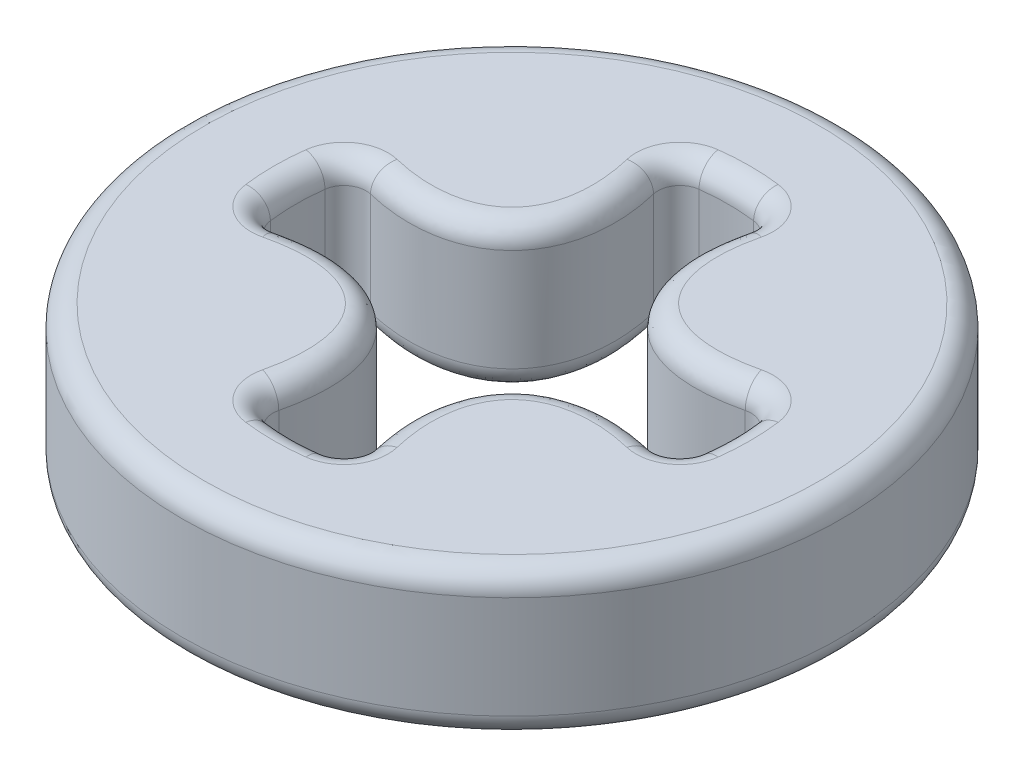
SolidWorks part; units mm, degrees
ref_plane "Front Plane" through (0, 0, 0) normal (0, 0, 1) x (1, 0, 0)
ref_plane "Top Plane" through (0, 0, 0) normal (0, 1, 0) x (1, 0, 0)
ref_plane "Right Plane" through (0, 0, 0) normal (1, 0, 0) x (0, 0, -1)
sketch "Sketch4" plane through (0, 0, 0) normal (0, 1, 0) x (1, 0, 0)
  circle A0 centre (0, 0) radius 4.5
extrude "Boss-Extrude3" add sketch "Sketch4" along normal blind 2
sketch "Sketch3" plane through (0, 0, 0) normal (0, 1, 0) x (1, 0, 0)
  arc A0 (0.7152, 2.862) -> (-0.7152, 2.862) centre (0, 0) ccw
  arc A1 (-2.862, 0.7152) -> (-2.862, -0.7152) centre (0, 0) ccw
  arc A2 (-0.7152, -2.862) -> (0.7152, -2.862) centre (0, 0) ccw
  arc A3 (2.862, -0.7152) -> (2.862, 0.7152) centre (0, 0) ccw
  ellipse E0 centre (-3.4, 3.4) end of major axis (-5.875, 5.875) minor radius 2 (-2.862, 0.7152) -> (-0.7152, 2.862) ccw
  ellipse E1 centre (3.4, 3.4) end of major axis (5.875, 5.875) minor radius 2 (0.7152, 2.862) -> (2.862, 0.7152) ccw
  ellipse E2 centre (3.4, -3.4) end of major axis (5.875, -5.875) minor radius 2 (2.862, -0.7152) -> (0.7152, -2.862) ccw
  ellipse E3 centre (-3.4, -3.4) end of major axis (-5.875, -5.875) minor radius 2 (-0.7152, -2.862) -> (-2.862, -0.7152) ccw
extrude "Cut-Extrude2" cut sketch "Sketch3" along normal blind 2
fillet "Fillet1" radius 0.3 26 edges at (0, 0, 2.95) (-0.925, 0, 0.925) (0.925, 2, 0.925) (0.925, 0, 0.925) (-2.95, 0, 0) (-2.95, 2, 0) (0, 2, 2.95) (2.95, 2, 0) (2.95, 0, 0) (0, 2, -2.95) (0, 0, -2.95) (0, 0, 4.5) (-2.862, 1, -0.7152) (-2.862, 1, 0.7152) (-0.7152, 1, 2.862) (0.7152, 1, 2.862) (2.862, 1, 0.7152) (2.862, 1, -0.7152) (0.7152, 1, -2.862) (-0.7152, 1, -2.862) (-0.925, 0, -0.925) (-0.925, 2, -0.925) (0.925, 2, -0.925) (0.925, 0, -0.925) (-0.925, 2, 0.925) (0, 2, 4.5)
